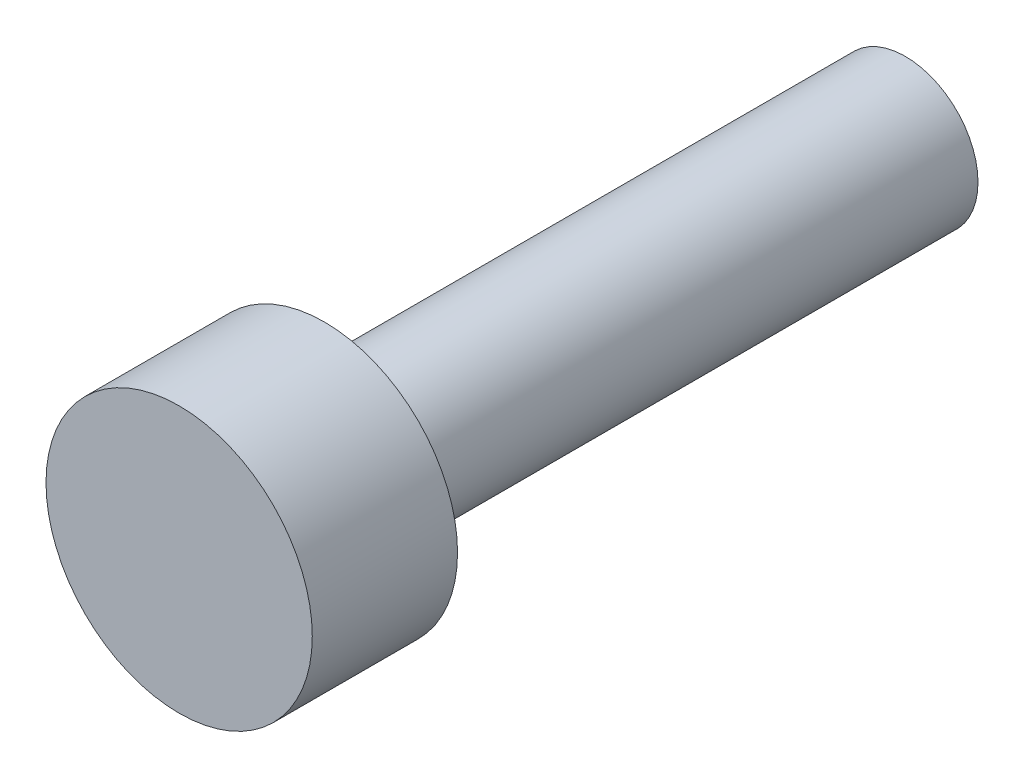
SolidWorks part; units mm, degrees
ref_plane "Front Plane" through (0, 0, 0) normal (0, 0, 1) x (1, 0, 0)
ref_plane "Top Plane" through (0, 0, 0) normal (0, 1, 0) x (1, 0, 0)
ref_plane "Right Plane" through (0, 0, 0) normal (1, 0, 0) x (0, 0, -1)
sketch "Shank_nominal_thread_envelope_profile" plane through (0, 0, 0) normal (0, 0, 1) x (1, 0, 0)
  circle A0 centre (0, 0) radius 1.5
  dimension "D1" = 3
extrude "Shank_nominal_thread_envelope" add sketch "Shank_nominal_thread_envelope_profile" along normal blind 12 from offset 12 offset against normal yes
sketch "Socket_head_envelope_profile" plane through (0, 0, 0) normal (0, 0, 1) x (1, 0, 0)
  circle A0 centre (0, 0) radius 2.75
  dimension "D1" = 5.5
extrude "Socket_head_envelope" add sketch "Socket_head_envelope_profile" along normal blind 3
